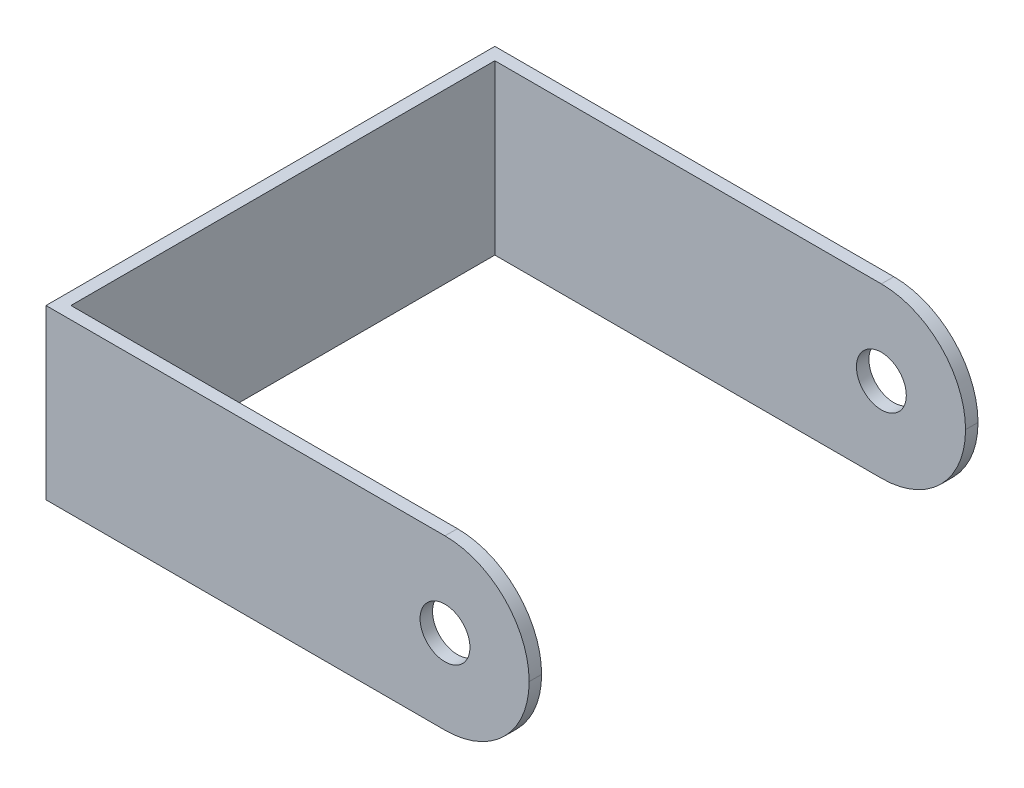
SolidWorks part; units mm, degrees
ref_plane "Front Plane" through (0, 0, 0) normal (0, 0, 1) x (1, 0, 0)
ref_plane "Top Plane" through (0, 0, 0) normal (0, 1, 0) x (1, 0, 0)
ref_plane "Right Plane" through (0, 0, 0) normal (1, 0, 0) x (0, 0, -1)
sketch "Sketch1" plane through (0, 0, 0) normal (0, 1, 0) x (1, 0, 0)
  line L1 (-273.1439, -461.3859) -> (-350.6439, -461.3859)
  line L2 (-273.1439, -461.3859) -> (-273.1439, -389.3859)
  line L3 (-273.1439, -389.3859) -> (-350.6439, -389.3859)
  line L4 (-350.6439, -461.3859) -> (-350.6439, -389.3859)
  line L5 (-273.1439, -461.3859) -> (-350.6439, -389.3859) construction
  line L6 (-273.1439, -389.3859) -> (-350.6439, -461.3859) construction
  dimension "D1" = 72
extrude "Boss-Extrude2" add sketch "Sketch1" along normal blind 27
sketch "Sketch2" plane through (0, 27, 0) normal (0, 1, 0) x (1, 0, 0)
  line L8 (-348.6439, -391.3859) -> (-348.6439, -459.3859)
  line L9 (-348.6439, -459.3859) -> (-275.1439, -459.3859)
  line L10 (-275.1439, -459.3859) -> (-275.1439, -391.3859)
  line L11 (-275.1439, -391.3859) -> (-348.6439, -391.3859)
  line L12 (-348.6439, -391.3859) -> (-348.6439, -459.3859)
  line L13 (-348.6439, -459.3859) -> (-275.1439, -459.3859)
  line L14 (-275.1439, -459.3859) -> (-275.1439, -391.3859)
  line L15 (-275.1439, -391.3859) -> (-348.6439, -391.3859)
  dimension "D1" = 2
extrude "Cut-Extrude1" cut sketch "Sketch2" against normal blind 27 contours L14 L15 L12 L13
sketch "Sketch7" plane through (0, 27, 0) normal (0, 1, 0) x (1, 0, 0)
  line L0 (-273.1439, -461.3859) -> (-273.1439, -389.3859) construction
  line L1 (-275.1439, -459.3859) -> (-273.1439, -459.3859)
  line L2 (-275.1439, -459.3859) -> (-275.1439, -391.3859)
  line L3 (-275.1439, -391.3859) -> (-273.1439, -391.3859)
  line L4 (-273.1439, -459.3859) -> (-273.1439, -391.3859)
extrude "Cut-Extrude2" cut sketch "Sketch7" against normal blind 27
fillet "Fillet6" radius 13.5 2 edges at (-273.1439, 0, 460.3859) (-273.1439, 27, 460.3859)
fillet "Fillet7" radius 13.5 2 edges at (-273.1439, 0, 390.3859) (-273.1439, 27, 390.3859)
sketch "Sketch9" plane through (0, 0, 461.3859) normal (0, 0, 1) x (1, 0, 0)
  circle A0 centre (-286.6439, 13.5) radius 4
extrude "Cut-Extrude3" cut sketch "Sketch9" against normal blind 94 contours A0
